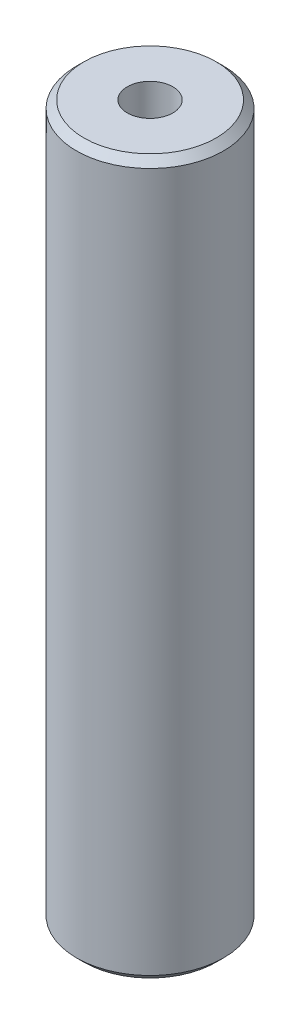
SolidWorks part; units mm, degrees
ref_plane "Front Plane" through (0, 0, 0) normal (0, 0, 1) x (1, 0, 0)
ref_plane "Top Plane" through (0, 0, 0) normal (0, 1, 0) x (1, 0, 0)
ref_plane "Right Plane" through (0, 0, 0) normal (1, 0, 0) x (0, 0, -1)
sketch "Sketch1" plane through (0, 0, 0) normal (0, 1, 0) x (1, 0, 0)
  circle A0 centre (0, 0) radius 42.5
  dimension "SHAFT_OD" = 85
extrude "Boss-Extrude1" add sketch "Sketch1" along normal blind 412.4337
sketch "Sketch2" plane through (0, 0, 0) normal (0, 1, 0) x (1, 0, 0)
  circle A0 centre (0, 0) radius 13.1412
  dimension "BORE_D" = 26.2825
extrude "Cut-Extrude1" cut sketch "Sketch2" along normal through all
chamfer "Chamfer1" distance 4.3124 angle 45 2 edges at (0, 412.4337, 42.5) (0, 0, 42.5)
